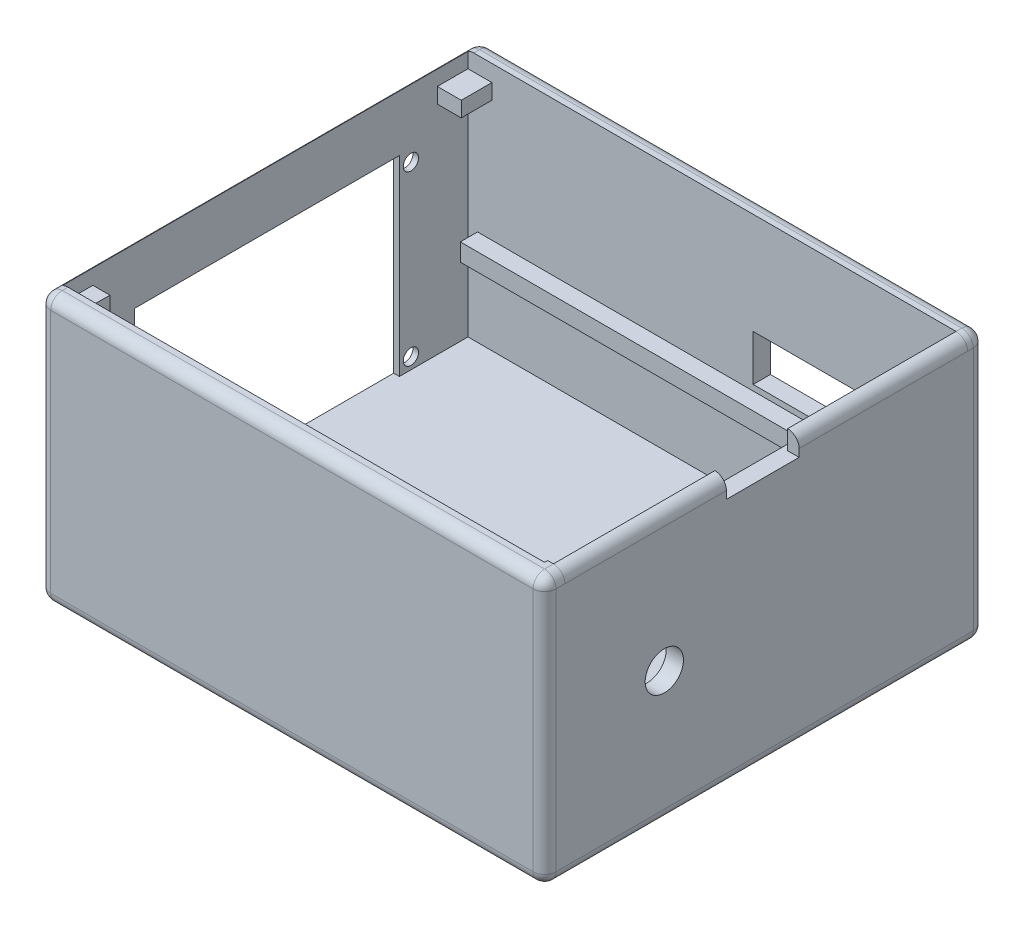
SolidWorks part; units mm, degrees
ref_plane "Front Plane" through (0, 0, 0) normal (0, 0, 1) x (1, 0, 0)
ref_plane "Top Plane" through (0, 0, 0) normal (0, 1, 0) x (1, 0, 0)
ref_plane "Right Plane" through (0, 0, 0) normal (1, 0, 0) x (0, 0, -1)
sketch "Sketch2" plane through (0, 0, 0) normal (0, 1, 0) x (1, 0, 0)
  line L0 (-63, 53) -> (-63, -53)
  line L1 (-67.5, 57.5) -> (67.5, 57.5)
  line L2 (-67.5, 57.5) -> (-67.5, -57.5)
  line L3 (-67.5, -57.5) -> (67.5, -57.5)
  line L4 (67.5, 57.5) -> (67.5, -57.5)
  line L5 (-67.5, 57.5) -> (67.5, -57.5) construction
  line L6 (-67.5, -57.5) -> (67.5, 57.5) construction
  line L7 (-63, -53) -> (63, -53)
  line L8 (63, 53) -> (63, -53)
  line L9 (-63, 53) -> (63, 53)
  point P0 (0, 0)
  dimension "D1" = 115
  dimension "D2" = 135
  dimension "D3" = 4.5
extrude "Boss-Extrude1" add sketch "Sketch2" along normal blind 70
extrude "Boss-Extrude2" add sketch "Sketch2<2>" along normal blind 5 contours L9 L0 L7 L8 region at (0, 0, 0)
sketch "Sketch2<2>" plane through (0, 0, 0) normal (0, 1, 0) x (1, 0, 0) same geometry as "Sketch2"
sketch "Sketch3" plane through (0, 0, -53) normal (0, 0, 1) x (1, 0, 0)
  line L1 (0, 0) -> (0, 70) construction
  line L2 (67.5, 0) -> (-67.5, 0) construction
  line L3 (63, 70) -> (-63, 70) construction
  line L4 (63, 70) -> (63, 5) construction
  line L5 (-60.5, 25.4157) -> (60.5, 25.4157)
  line L6 (-60.5, 25.4157) -> (-60.5, 30)
  line L7 (-60.5, 30) -> (60.5, 30)
  line L8 (60.5, 25.4157) -> (60.5, 30)
  line L9 (-60.5, 25.4157) -> (60.5, 30) construction
  line L10 (-60.5, 30) -> (60.5, 25.4157) construction
  line L11 (-63, 5) -> (63, 5) construction
  line L12 (-63, 70) -> (-63, 5) construction
  line L13 (11.5, 43.5) -> (46.5, 43.5)
  line L14 (11.5, 43.5) -> (11.5, 31.5)
  line L15 (11.5, 31.5) -> (46.5, 31.5)
  line L16 (46.5, 43.5) -> (46.5, 31.5)
  line L17 (11.5, 43.5) -> (46.5, 31.5) construction
  line L18 (11.5, 31.5) -> (46.5, 43.5) construction
  point P1 (0, 27.7078)
  point P16 (29, 37.5)
  dimension "D1" = 25
  dimension "D2" = 121
  dimension "D3" = 35
  dimension "D4" = 12
  dimension "D5" = 75
  dimension "D6" = 13.5
extrude "Boss-Extrude3" add sketch "Sketch3" along normal blind 4.5 contours L5 L8 L7 L6
extrude "Cut-Extrude1" cut sketch "Sketch3<3>" against normal through all contours L16 L13 L14 L15 region at (29, 37.5, -53)
sketch "Sketch3<3>" plane through (0, 0, -53) normal (0, 0, 1) x (1, 0, 0) same geometry as "Sketch3"
sketch "Sketch10" plane through (0, 0, 57.5) normal (0, 0, 1) x (1, 0, 0)
  circle A0 centre (-37.7153, 36.3262) radius 4.25
sketch "Sketch11" plane through (-67.5, 0, 0) normal (-1, 0, 0) x (0, 0, 1)
  line L0 (-57.5, 70) -> (-57.5, 0) construction
  line L1 (-41.1, 5) -> (39.9, 5)
  line L2 (-41.1, 5) -> (-41.1, 55)
  line L3 (-41.1, 55) -> (39.9, 55)
  line L4 (39.9, 5) -> (39.9, 55)
  line L7 (-35.1, 55) -> (34.1, 55)
  line L8 (-35.1, 55) -> (-35.1, 5)
  line L9 (-35.1, 5) -> (34.1, 5)
  line L14 (0, 0) -> (0, 70) construction
  line L15 (-57.5, 0) -> (57.5, 0) construction
  line L16 (-57.5, 70) -> (57.5, 70) construction
  line L19 (34.1, 55) -> (34.1, 5)
  line L21 (-41.1, 30) -> (39.9, 30) construction
  circle A4 centre (-38.1, 52) radius 2
  circle A5 centre (38.1, 52) radius 2
  circle A6 centre (38.1, 8) radius 2
  circle A7 centre (-38.1, 8) radius 2
  point P0 (0, 29.9383)
  dimension "D2" = 3
  dimension "D3" = 69.2
  dimension "D1" = 3
  dimension "D5" = 81
  dimension "D4" = 22.4
  dimension "D7" = 4
  dimension "D6" = 3
extrude "Cut-Extrude3" cut sketch "Sketch11" against normal blind 26.5 contours L19 L3 L8 L1 | A7 | A5 | A6 | A4 region at (-67.5, 30, -0.5) region at (-67.5, 8, 38.0642) region at (-67.5, 52, 38.0642) region at (-67.5, 8, -38.1)
sketch "Sketch12" plane through (0, 70, 0) normal (0, 1, 0) x (1, 0, 0)
  line L0 (67.5, -57.5) -> (67.5, 57.5) construction
  line L3 (60.5, -52.1714) -> (67.5, -52.1714)
  line L5 (63, 53) -> (67.5, 53)
  line L6 (63, 53) -> (63, -53)
  line L7 (63, -53) -> (67.5, -53)
  line L8 (67.5, 53) -> (67.5, -53)
  line M5 (67.5, -57.5) -> (67.5, 57.5)
  line M11 (63, 53) -> (63, -53)
sketch "Sketch21" plane through (67.5, 0, 0) normal (1, 0, 0) x (0, 0, -1)
  circle A0 centre (-26.2093, 34.3164) radius 5
extrude "Cut-Extrude7" cut sketch "Sketch21" against normal blind 10 contours A0
extrude "Cut-Extrude4" cut sketch "Sketch12" against normal blind 5 contours L7 L5 M11 M5 region at (65.25, 70, -0.4143)
sketch "Sketch13" plane through (0, 60, 0) normal (0, 1, 0) x (1, 0, 0)
  line L1 (67.5, 45) -> (60.5, 45) construction
  line L5 (67.5, 45) -> (64, 45)
  line L7 (64, 45) -> (67.5, 45)
  line L8 (64, 45) -> (64, -50.5)
  line L9 (64, -50.5) -> (67.5, -50.5)
  line L10 (67.5, 45) -> (67.5, -50.5)
sketch "Sketch15" plane through (-67.5, 0, 0) normal (-1, 0, 0) x (0, 0, 1)
  line L1 (-57.5, 0) -> (57.5, 0)
  line L2 (-57.5, 0) -> (-57.5, 70)
  line L3 (-57.5, 70) -> (57.5, 70)
  line L4 (57.5, 0) -> (57.5, 70)
extrude "Cut-Extrude6" cut sketch "Sketch15" against normal blind 3
sketch "Sketch16" plane through (0, 5, 0) normal (0, 1, 0) x (1, 0, 0)
  line L0 (-63, 0) -> (60.5, 0) construction
  line L1 (-63, 53) -> (-63, -53) construction
  line L2 (60.5, 45) -> (60.5, -45) construction
sketch "Sketch17" plane through (0, 0, 53) normal (0, 0, -1) x (-1, 0, 0)
  line L0 (0, 0) -> (0, 70) construction
  line L1 (-60.3877, 30) -> (60.5375, 30)
  line L2 (-60.3877, 30) -> (-60.3877, 25.5)
  line L3 (-60.3877, 25.5) -> (60.5375, 25.5)
  line L4 (60.5375, 30) -> (60.5375, 25.5)
  line L5 (63, 70) -> (-63, 70) construction
  point P12 (0, 4.8129)
  dimension "D1" = 4.5
  dimension "D2" = 25.5
extrude "Boss-Extrude5" add sketch "Sketch17" along normal blind 5.5 contours L2 L1 L4 L3
sketch "Sketch18" plane through (0, 0, 0) normal (1, 0, 0) x (0, 0, -1)
fillet "Fillet1" radius 3 3 edges at (67.5, 0, 0) (1.5, 0, 57.5) (1.5, 0, -57.5)
fillet "Fillet2" radius 3 9 edges at (66.6213, 0.8787, -56.6213) (-64.5, 36.5, -57.5) (-64.5, 0.8787, -56.6213) (-64.5, 0, 0) (-64.5, 0.8787, 56.6213) (66.6213, 0.8787, 56.6213) (67.5, 36.5, -57.5) (-64.5, 36.5, 57.5) (67.5, 36.5, 57.5)
fillet "Fillet3" radius 3 9 edges at (67.5, 70, -53.75) (66.6213, 70, -56.6213) (1.5, 70, -57.5) (-63.6213, 70, -56.6213) (-64.5, 70, 0) (-63.6213, 70, 56.6213) (1.5, 70, 57.5) (66.6213, 70, 56.6213) (67.5, 70, 53.3357)
sketch "Sketch22" plane through (0, 65, 0) normal (0, 1, 0) x (1, 0, 0)
  line L1 (64.5, 53) -> (67.5, 53)
  line L2 (64.5, 53) -> (64.5, -52.1714)
  line L3 (64.5, -52.1714) -> (67.5, -52.1714)
  line L4 (67.5, 53) -> (67.5, -52.1714)
extrude "Boss-Extrude8" add sketch "Sketch22" along normal blind 5
sketch "Sketch14" plane through (67.5, 0, 0) normal (1, 0, 0) x (0, 0, -1)
  line L0 (-10, 70) -> (9, 70)
  line L1 (-57.5, 70) -> (57.5, 70) construction
  line L2 (9, 70) -> (9, 65)
  line L3 (9, 65) -> (-10, 65)
  line L4 (-10, 65) -> (-10, 70)
  line L5 (-57.5, 70) -> (-57.5, 0) construction
  point P5 (-0.5, 70)
  dimension "D1" = 47.5
  dimension "D2" = 5
  dimension "D3" = 19
extrude "Cut-Extrude5" cut sketch "Sketch14" against normal blind 5
sketch "Sketch19" plane through (0, 0, -53) normal (0, 0, 1) x (1, 0, 0)
  line L0 (-63, 69.5981) -> (-63, 5) construction
  line L1 (-63, 65.6699) -> (-56.7558, 65.6699)
  line L2 (-63, 65.6699) -> (-63, 61.6699)
  line L3 (-63, 61.6699) -> (-56.7558, 61.6699)
  line L4 (-56.7558, 65.6699) -> (-56.7558, 61.6699)
  dimension "D1" = 5
  dimension "D2" = 4
extrude "Boss-Extrude6" add sketch "Sketch19" along normal blind 8
sketch "Sketch20" plane through (0, 0, 53) normal (0, 0, -1) x (-1, 0, 0)
  line L0 (63, 69.5981) -> (63, 5) construction
  line L1 (63, 65.6699) -> (58.5522, 65.6699)
  line L2 (63, 65.6699) -> (63, 55.348)
  line L3 (63, 55.348) -> (58.5522, 55.348)
  line L4 (58.5522, 65.6699) -> (58.5522, 55.348)
  dimension "D1" = 5
  dimension "D2" = 4.4478
extrude "Boss-Extrude7" add sketch "Sketch20" along normal blind 8
fillet "Fillet5" radius 3 1 edges at (67.5, 70, 31.0857)
fillet "Fillet6" radius 3 1 edges at (67.5, 70, -31)
